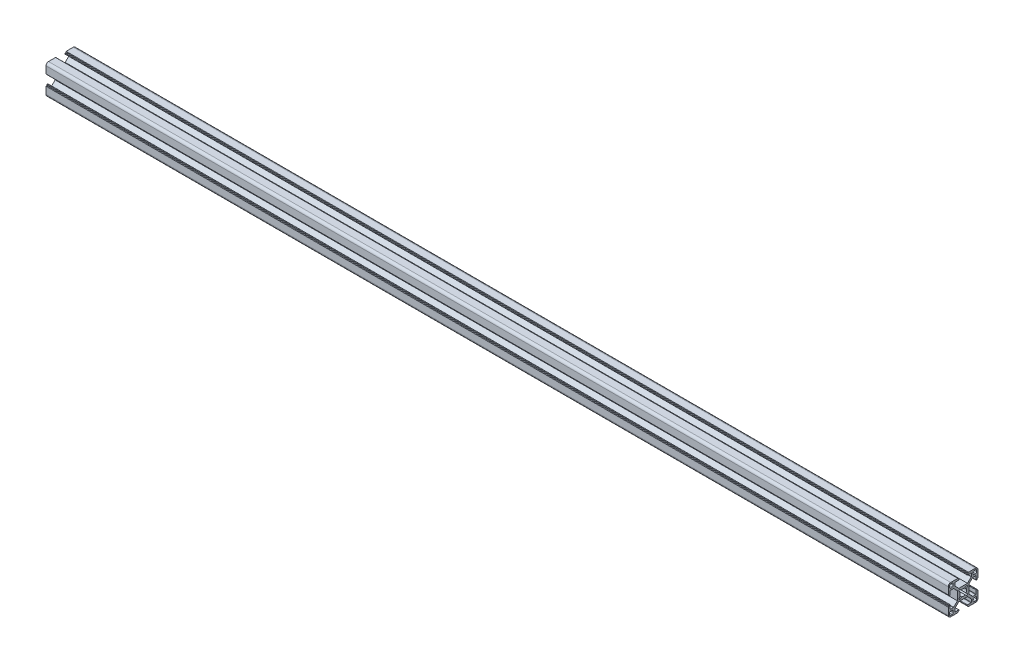
SolidWorks part; units mm, degrees
material "2.0572 (CuZn40Mn2Fe1)"
ref_plane "Front Plane" through (0, 0, 0) normal (0, 0, 1) x (1, 0, 0)
ref_plane "Top Plane" through (0, 0, 0) normal (0, 1, 0) x (1, 0, 0)
ref_plane "Right Plane" through (0, 0, 0) normal (1, 0, 0) x (0, 0, -1)
ref_axis "Axis_X" through (-58.3, 0, 0) along (1, 0, 0)
ref_axis "Axis_Y" through (0, 38.5, 0) along (0, -1, 0)
ref_axis "Axis_Z" through (0, 0, -4.5) along (0, 0, 1)
sketch "Sketch2" plane through (0, 0, 0) normal (1, 0, 0) x (0, 0, -1)
  line L1 (-15, 15) -> (15, 15)
  line L2 (-15, 15) -> (-15, -15)
  line L3 (-15, -15) -> (15, -15)
  line L4 (15, 15) -> (15, -15)
  line L5 (-15, 15) -> (15, -15) construction
  line L6 (-15, -15) -> (15, 15) construction
  point P0 (0, 0)
  dimension "D1" = 30
  dimension "D2" = 30
extrude "Boss-Extrude1" add sketch "Sketch2" along normal blind 910
sketch "Sketch5" plane through (910, 0, 0) normal (1, 0, 0) x (0, 0, -1)
  circle A0 centre (0, 0) radius 3.4
  dimension "D1" = 6.8
extrude "Cut-Extrude2" cut sketch "Sketch5" against normal through all
sketch "Sketch4" plane through (910, 0, 0) normal (1, 0, 0) x (0, 0, -1)
  line L0 (-4.3858, -5.8) -> (4.3858, -5.8)
  line L1 (4.3858, -5.8) -> (8.1621, -9.5763)
  line L2 (8.25, -9.7885) -> (8.25, -13)
  line L3 (8.25, -13) -> (4.1, -13)
  line L4 (4.1, -13) -> (4.1, -14)
  line L5 (4.1, -14) -> (5.1, -14)
  line L6 (5.1, -14) -> (5.1, -15)
  line L7 (-15, -15) -> (15, -15) construction
  line L8 (5.1, -15) -> (-5.1, -15)
  line L9 (-5.1, -15) -> (-5.1, -14)
  line L10 (-5.1, -14) -> (-4.1, -14)
  line L11 (-4.1, -14) -> (-4.1, -13)
  line L12 (-4.1, -13) -> (-8.25, -13)
  line L13 (-8.25, -13) -> (-8.25, -9.7885)
  line L14 (-8.1621, -9.5763) -> (-4.3858, -5.8)
  line L16 (-4.1, -13) -> (4.1, -13) construction
  line L17 (0, -14) -> (0, -15) construction
  line L18 (-4.1, -14) -> (4.1, -14) construction
  line L19 (0, -5.8) -> (0, -13) construction
  line L20 (0, -13) -> (0, -14) construction
  line L21 (15, -15) -> (15, 15) construction
  line L22 (11.05, -10.05) -> (12.65, -10.05)
  line L23 (10.05, -11.05) -> (10.05, -12.65)
  line L24 (11.05, -13.65) -> (12.65, -13.65)
  line L25 (13.65, -11.05) -> (13.65, -12.65)
  line L26 (10.05, -10.05) -> (13.65, -13.65) construction
  line L27 (10.05, -13.65) -> (13.65, -10.05) construction
  line L28 (0, 0) -> (3.5355, -3.5355) construction
  line L29 (15, -15) -> (15, 15) construction
  line L30 (4.0659, -3.0052) -> (2.8753, -1.8146)
  line L31 (3.0052, -4.0659) -> (1.8146, -2.8753)
  arc A0 (12.65, -13.65) -> (13.65, -12.65) centre (12.65, -12.65) ccw
  arc A1 (11.05, -13.65) -> (10.05, -12.65) centre (11.05, -12.65) cw
  arc A2 (10.05, -11.05) -> (11.05, -10.05) centre (11.05, -11.05) cw
  arc A3 (12.65, -10.05) -> (13.65, -11.05) centre (12.65, -11.05) cw
  arc A4 (3.0052, -4.0659) -> (4.0659, -3.0052) centre (3.5355, -3.5355) ccw
  circle A5 centre (0, 0) radius 3.4 construction
  arc A6 (1.8146, -2.8753) -> (2.8753, -1.8146) centre (0, 0) ccw
  arc A7 (-8.25, -9.7885) -> (-8.1621, -9.5763) centre (-7.95, -9.7885) cw
  arc A8 (8.25, -9.7885) -> (8.1621, -9.5763) centre (7.95, -9.7885) ccw
  point P18 (11.85, -11.85)
  point P47 (-8.25, -9.6642)
  point P55 (8.25, -9.6642)
  dimension "D11" = 1
  dimension "D14" = 1.5
  dimension "D2" = 0.3
  dimension "D1" = 9.2
  dimension "D3" = 1
  dimension "D4" = 8.2
  dimension "D5" = 10.2
  dimension "D6" = 16.5
  dimension "D7" = 2
  dimension "D8" = 1.35
  dimension "D9" = 1.35
  dimension "D10" = 3.6
  dimension "D12" = 45
  dimension "D13" = 5
  dimension "D15" = 5.4237
extrude "Cut-Extrude1" cut sketch "Sketch4" against normal through all
fillet "Fillet1" radius 2.5 1 edges at (455, -15, -15)
fillet "Fillet2" radius 0.3 10 edges at (455, -14, -5.1) (455, -15, -5.1) (455, -14, -4.1) (455, -13, -4.1) (455, -13, -8.25) (455, -13, 8.25) (455, -13, 4.1) (455, -14, 4.1) (455, -14, 5.1) (455, -15, 5.1)
pattern_circular "CirPattern1" count 4 over 360 about axis through (0, 0, 0) along (1, 0, 0) of "Cut-Extrude1", "Fillet1", "Fillet2"
equation "\"Factor\"= 1.082532"
